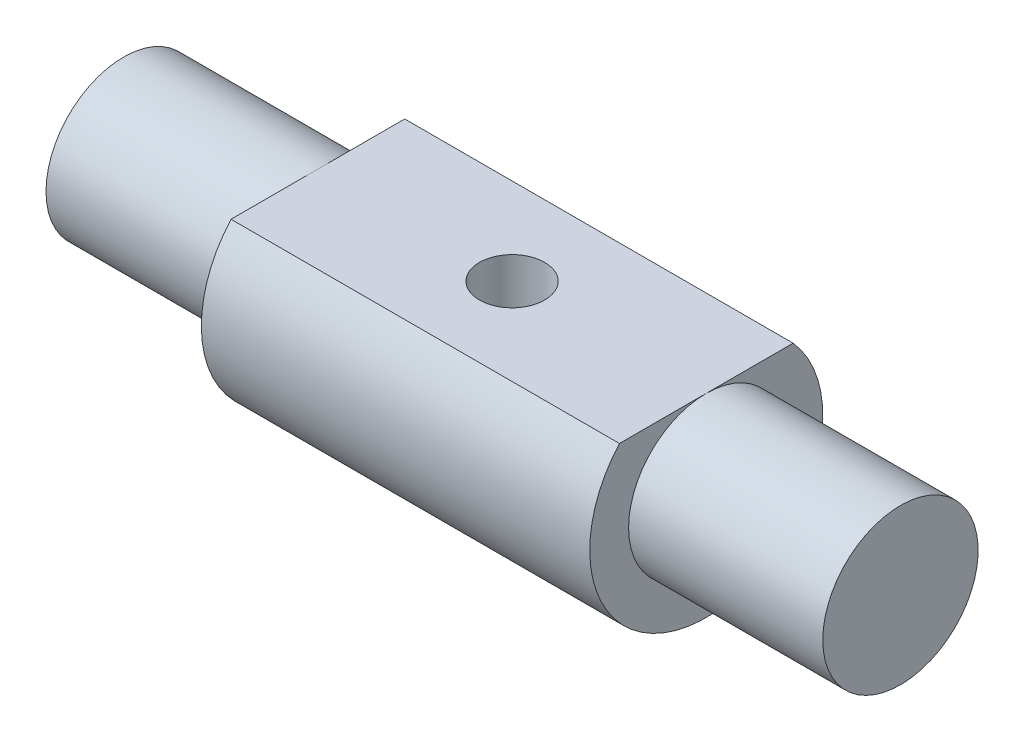
SolidWorks part; units mm, degrees
ref_plane "前视基准面" through (0, 0, 0) normal (0, 0, 1) x (1, 0, 0)
ref_plane "上视基准面" through (0, 0, 0) normal (0, 1, 0) x (1, 0, 0)
ref_plane "右视基准面" through (0, 0, 0) normal (1, 0, 0) x (0, 0, -1)
sketch "草图1" plane through (0, 0, 0) normal (0, 0, 1) x (1, 0, 0)
  line L0 (0, 0) -> (0, 73.8056) construction
  line L1 (0, -6.875) -> (0, 6.875) construction
  line L2 (0, 7.5) -> (12.5, 7.5)
  line L3 (12.5, 7.5) -> (12.5, 5)
  line L4 (12.5, 5) -> (25, 5)
  line L5 (25, 5) -> (25, 0)
  line L6 (12.7722, 0) -> (-12.7722, 0) construction
  line L7 (25, 0) -> (0, 0) construction
  line L8 (0, 7.5) -> (0, 0)
  line L9 (0, 0) -> (25, 0)
  dimension "D1" = 10
  dimension "D2" = 15
  dimension "D3" = 25
  dimension "D4" = 50
revolve "旋转1" add sketch "草图1" angle 360 about L9
mirror "镜向1" about plane through (0, 0, 0) normal (1, 0, 0) of "旋转1"
ref_axis "基准轴1" through (25, 0, 0) along (-1, 0, 0)
sketch "草图2" plane through (0, 0, 0) normal (0, 1, 0) x (1, 0, 0)
  line L1 (-12.5, -11.6111) -> (12.5, -11.6111)
  line L2 (-12.5, -11.6111) -> (-12.5, 11.6111)
  line L3 (-12.5, 11.6111) -> (12.5, 11.6111)
  line L4 (12.5, -11.6111) -> (12.5, 11.6111)
  line L5 (-12.5, -11.6111) -> (12.5, 11.6111) construction
  line L6 (-12.5, 11.6111) -> (12.5, -11.6111) construction
  point P0 (0, 0)
  dimension "D1" = 25
extrude "切除-拉伸1" cut sketch "草图2" along normal through all from offset 5
hole_wizard "M5 螺纹孔的螺纹孔钻头1" positions "草图4" profile "草图5" hole size "M5" standard "GB" end condition up to next
sketch "草图4" plane through (0, 5, 0) normal (0, 1, 0) x (1, 0, 0)
  point P0 (0, 0)
sketch "草图5" plane through (0, 5, 0) normal (1, 0, 0) x (0, 0, 1)
  line L0 (0, 0) -> (0, 12.5)
  line L1 (0, 12.5) -> (2.1, 12.5)
  line L2 (2.1, 12.5) -> (2.1, 0)
  line L5 (2.1, 0) -> (0, 0)
  line L11 (0, -6.35) -> (0, 107.95) construction
  dimension "通孔孔直径" = 4.2
  dimension "通孔孔深度" = 12.5
